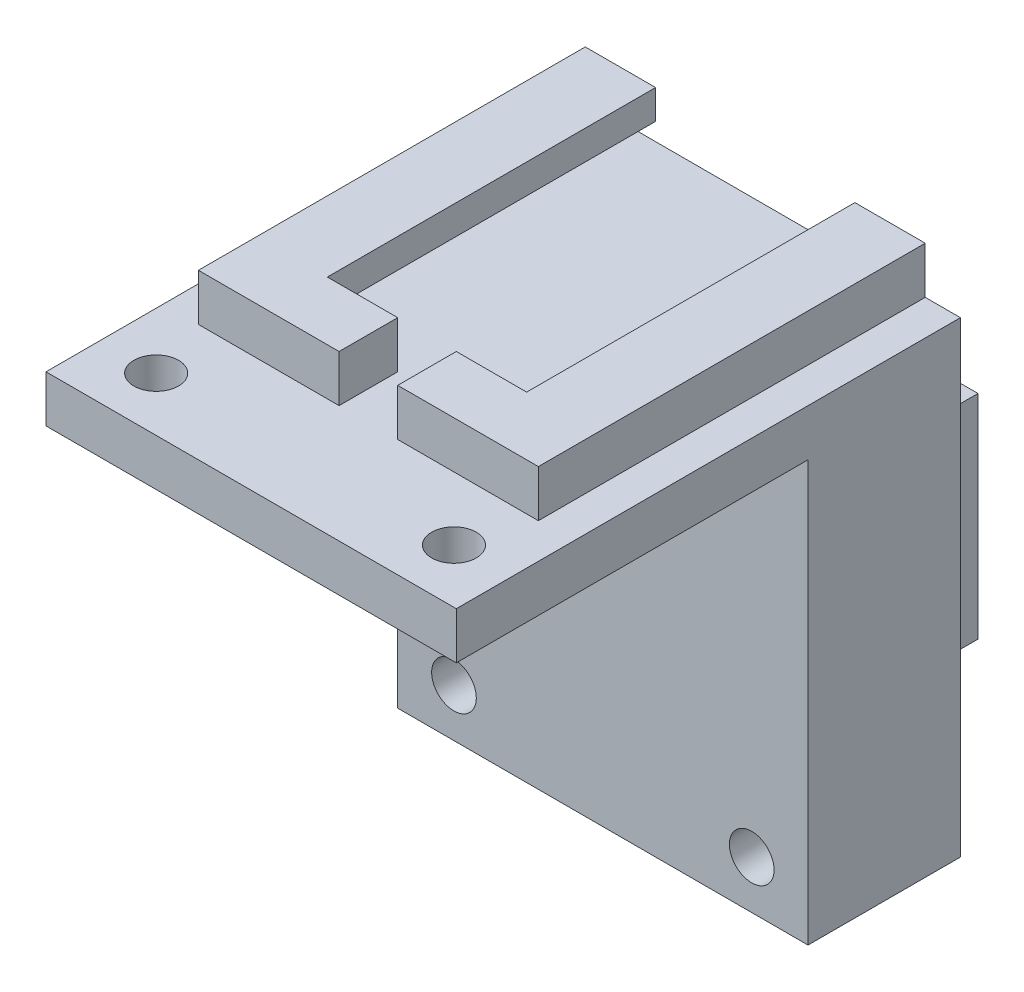
SolidWorks part; units mm, degrees
ref_plane "Front Plane" through (0, 0, 0) normal (0, 0, 1) x (1, 0, 0)
ref_plane "Top Plane" through (0, 0, 0) normal (0, 1, 0) x (1, 0, 0)
ref_plane "Right Plane" through (0, 0, 0) normal (1, 0, 0) x (0, 0, -1)
sketch "Sketch1" plane through (0, 0, 0) normal (0, 1, 0) x (1, 0, 0)
  line L1 (0, 0) -> (29, 0)
  line L2 (0, 0) -> (0, 15)
  line L3 (0, 15) -> (29, 15)
  line L4 (29, 0) -> (29, 15)
  dimension "D1" = 29
  dimension "D2" = 15
extrude "Boss-Extrude1" add sketch "Sketch1" along normal blind 8
sketch "Sketch2" plane through (0, 0, 0) normal (0, 0, 1) x (1, 0, 0)
  line L0 (0, 0) -> (29, 0) construction
  line L1 (4, 5.5) -> (25, 5.5)
  line L2 (4, 5.5) -> (4, 3.5)
  line L3 (4, 3.5) -> (25, 3.5)
  line L4 (25, 5.5) -> (25, 3.5)
  line L5 (0, 8) -> (29, 8) construction
  line L6 (6, 8) -> (23, 8)
  line L7 (6, 8) -> (6, 5.5)
  line L8 (6, 5.5) -> (23, 5.5)
  line L9 (23, 8) -> (23, 5.5)
  line L10 (0, 8) -> (0, 0) construction
  point P12 (14.5, 0)
  point P13 (14.5, 3.5)
  point P14 (14.5, 8)
  line M11 (29, 8) -> (0, 8)
  dimension "D1" = 3.5
  dimension "D2" = 2
  dimension "D3" = 6
  dimension "D4" = 4
extrude "Cut-Extrude1" cut sketch "Sketch2" against normal through all both and the other way through all contours L9 L7 L1 M11 | L4 L1 L2 L3 region at (14.5, 4.5, 0) region at (14.5, 6.75, 0)
sketch "Sketch4" plane through (0, 0, 0) normal (0, 0, 1) x (1, 0, 0)
  line L1 (0, 8) -> (29, 8)
  line L2 (0, 8) -> (0, 0)
  line L3 (0, 0) -> (29, 0)
  line L4 (29, 8) -> (29, 0)
  line L5 (12, 8) -> (17, 8)
  line L6 (12, 8) -> (12, 0)
  line L7 (12, 0) -> (17, 0)
  line L8 (17, 8) -> (17, 0)
  point P10 (14.5, 8)
  point P11 (14.5, 8)
  line M1 (23, 8) -> (23, 5.5)
  line M2 (23, 5.5) -> (25, 5.5)
  line M3 (25, 5.5) -> (25, 3.5)
  line M4 (25, 3.5) -> (4, 3.5)
  line M5 (4, 3.5) -> (4, 5.5)
  line M6 (4, 5.5) -> (6, 5.5)
  line M7 (6, 5.5) -> (6, 8)
  line M8 (6, 8) -> (0, 8)
  line M9 (0, 8) -> (0, 0)
  line M10 (0, 0) -> (29, 0)
  line M11 (29, 0) -> (29, 8)
  line M12 (29, 8) -> (23, 8)
  dimension "D1" = 5
extrude "Boss-Extrude2" add sketch "Sketch4" along normal blind 5 contours L8 L6 L3 M4 | L8 M4 M10 M11 M12 M1 M2 M3 | L6 M4 M5 M6 M7 M8 M9 M10 | L6 L1 M7 M6 M5 M4 | L1 L8 M4 M3 M2 M1 region at (4.8154, 3.2423, 0) region at (8.4839, 5.5887, 0) region at (14.5, 1.75, 0) region at (20.5161, 5.5887, 0) region at (24.1846, 3.2423, 0)
sketch "Sketch5" plane through (0, 0, 0) normal (0, -1, 0) x (-1, 0, 0)
  line L0 (-29, 15) -> (0, 15) construction
  line L1 (3, 15) -> (-32, 15)
  line L2 (3, 15) -> (3, -15)
  line L3 (3, -15) -> (-32, -15)
  line L4 (-32, 15) -> (-32, -15)
  line L5 (0, -5) -> (-29, -5) construction
  point P8 (-14.5, -5)
  point P9 (-14.5, -15)
  dimension "D1" = 35
  dimension "D2" = 30
extrude "Boss-Extrude3" add sketch "Sketch5" against normal blind 4
sketch "Sketch6" plane through (0, 0, 0) normal (0, -1, 0) x (-1, 0, 0)
  line L0 (-32, -15) -> (3, -15) construction
  line L1 (-1.8, -10.4) -> (-27.2, -10.4) construction
  line L2 (-1.8, -10.4) -> (-1.8, 2.3) construction
  line L3 (-1.8, 2.3) -> (-27.2, 2.3) construction
  line L4 (-27.2, -10.4) -> (-27.2, 2.3) construction
  line L5 (-32, 15) -> (3, 15) construction
  circle A0 centre (-1.8, 2.3) radius 1.905
  circle A1 centre (-27.2, -10.4) radius 1.905
  circle A2 centre (-1.8, -10.4) radius 1.905
  circle A3 centre (-27.2, 2.3) radius 1.905
  point P16 (-14.5, -15)
  point P17 (-14.5, -10.4)
  dimension "D2" = 3.81
  dimension "D1" = 25.4
  dimension "D3" = 12.7
  dimension "D4" = 12.7
extrude "Cut-Extrude2" cut sketch "Sketch6" against normal through all both contours A1 | A2
sketch "Sketch9" plane through (0, 0, -15) normal (0, 0, -1) x (-1, 0, 0)
  line L1 (-32, 4) -> (3, 4)
  line L2 (-32, 4) -> (-32, -35.85)
  line L3 (-32, -35.85) -> (3, -35.85)
  line L4 (3, 4) -> (3, -35.85)
  dimension "D1" = 39.85
  dimension "D2" = 35
extrude "Boss-Extrude4" add sketch "Sketch9" along normal blind 13
sketch "Sketch10" plane through (0, 0, -15) normal (0, 0, 1) x (1, 0, 0)
  line L1 (32, -35.85) -> (-3, -35.85) construction
  line L2 (1.8, -19.05) -> (27.2, -19.05) construction
  line L3 (1.8, -19.05) -> (1.8, -31.75) construction
  line L4 (1.8, -31.75) -> (27.2, -31.75) construction
  line L5 (27.2, -19.05) -> (27.2, -31.75) construction
  line L6 (32, 0) -> (-3, 0) construction
  circle A0 centre (1.8, -19.05) radius 1.905
  circle A1 centre (27.2, -19.05) radius 1.905
  circle A2 centre (1.8, -31.75) radius 1.905
  circle A3 centre (27.2, -31.75) radius 1.905
  point P13 (14.5, -35.85)
  point P14 (14.5, -31.75)
  dimension "D1" = 3.81
  dimension "D2" = 19.05
  dimension "D3" = 12.7
  dimension "D4" = 25.4
extrude "Cut-Extrude4" cut sketch "Sketch10" against normal up to surface (13 mm away) contours A3 | A2 up to face at (14.5, -15.925, -28)
sketch "Sketch11" plane through (0, 0, -28) normal (0, 0, -1) x (-1, 0, 0)
  line L0 (3, 4) -> (-32, 4) construction
  line L1 (0, -5.35) -> (-29, -5.35)
  line L2 (0, -5.35) -> (0, -18.5)
  line L3 (0, -18.5) -> (-29, -18.5)
  line L4 (-29, -5.35) -> (-29, -18.5)
  line L5 (-32, -35.85) -> (3, -35.85) construction
  point P6 (-14.5, -35.85)
  point P9 (-14.5, -18.5)
  dimension "D1" = 22.5
  dimension "D2" = 9.35
  dimension "D3" = 29
extrude "Boss-Extrude5" add sketch "Sketch11" along normal blind 4.5
sketch "Sketch12" plane through (0, -5.35, 0) normal (0, 1, 0) x (1, 0, 0)
  line L0 (0, 28) -> (29, 28) construction
  line L1 (4, 28) -> (25, 28)
  line L2 (4, 28) -> (4, 30)
  line L3 (4, 30) -> (25, 30)
  line L4 (25, 28) -> (25, 30)
  line L5 (6, 30) -> (23, 30)
  line L6 (6, 30) -> (6, 32.5)
  line L7 (6, 32.5) -> (23, 32.5)
  line L8 (23, 30) -> (23, 32.5)
  line L9 (0, 32.5) -> (29, 32.5) construction
  line L10 (29, 32.5) -> (29, 28) construction
  point P10 (14.5, 28)
  point P11 (14.5, 28)
  point P12 (14.5, 30)
  line M9 (0, 28) -> (29, 28)
  line M11 (29, 32.5) -> (0, 32.5)
  dimension "D1" = 2
  dimension "D2" = 6
  dimension "D3" = 4
extrude "Cut-Extrude5" cut sketch "Sketch12" along direction (0, 1, 0) on the side against the normal through all contours L4 L3 L2 M9 | L3 L8 L6 M11 region at (14.5, -5.35, -29) region at (14.5, -5.35, -31.25)
sketch "Sketch13" plane through (0, -18.5, 0) normal (0, -1, 0) x (-1, 0, 0)
  line L0 (0, 32.5) -> (0, 28) construction
  line L1 (0, 28) -> (-29, 28)
  line L2 (0, 28) -> (0, 32.5)
  line L3 (0, 32.5) -> (-29, 32.5)
  line L4 (-29, 28) -> (-29, 32.5)
  line L5 (-12, 32.5) -> (-17, 32.5)
  line L6 (-12, 32.5) -> (-12, 28)
  line L7 (-12, 28) -> (-17, 28)
  line L8 (-17, 32.5) -> (-17, 28)
  line L10 (-4, 28) -> (0, 28) construction
  point P11 (-14.5, 28)
  point P12 (-14.5, 28)
  point P16 (-12, 29.3948)
  line M1 (-4, 30) -> (-4, 28)
  line M2 (-4, 28) -> (0, 28)
  line M3 (0, 28) -> (0, 32.5)
  line M4 (0, 32.5) -> (-6, 32.5)
  line M5 (-6, 32.5) -> (-6, 30)
  line M6 (-6, 30) -> (-4, 30)
  dimension "D1" = 5
extrude "Boss-Extrude6" add sketch "Sketch13" along normal blind 5 contours M6 M1 M2 M3 M4 M5 | L6 L1 M6 M1 | L8 L3 L4 L1 region at (2.6522, -18.5, -30.4674) region at (8.4839, -18.5, -30.0887) region at (23, -18.5, -30.25)
sketch "Sketch14" plane through (0, 0, -15) normal (0, 0, -1) x (-1, 0, 0)
  line L0 (-6, 8) -> (-6, 5.5) construction
  line L1 (0, 8) -> (-29, 8)
  line L2 (0, 8) -> (0, 4)
  line L3 (0, 4) -> (-29, 4)
  line L4 (-29, 8) -> (-29, 4)
  line L5 (-4, 4) -> (-25, 4)
  line L6 (-4, 4) -> (-4, 5.5)
  line L7 (-4, 5.5) -> (-25, 5.5)
  line L8 (-25, 4) -> (-25, 5.5)
  line L9 (-23, 8) -> (-6, 8)
  line L10 (-23, 8) -> (-23, 5.5)
  line L11 (-23, 5.5) -> (-6, 5.5)
  line L12 (-6, 8) -> (-6, 5.5)
  line M5 (-4, 4) -> (0, 4)
  line M6 (0, 4) -> (0, 8)
  line M7 (0, 8) -> (-6, 8)
  line M8 (-6, 8) -> (-6, 5.5)
  line M9 (-6, 5.5) -> (-4, 5.5)
  line M10 (-4, 5.5) -> (-4, 4)
extrude "Boss-Extrude7" add sketch "Sketch14" along normal up to surface (13 mm away) contours M10 M5 M6 M7 M8 M9 | L10 L1 L4 L3 L8 L7 region at (2.7143, 6.1786, -15) region at (26.2857, 6.1786, -15) up to face at (23.6667, -15.7833, -28)
